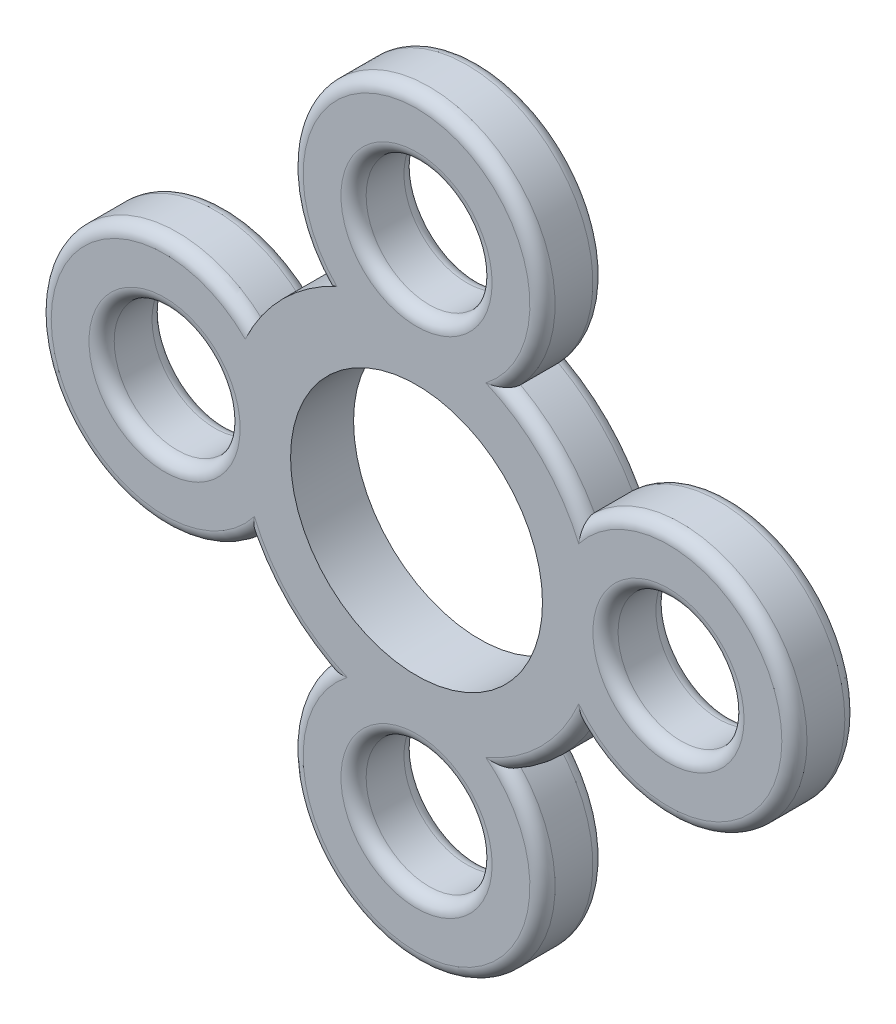
SolidWorks part; units mm, degrees
ref_plane "Front Plane" through (0, 0, 0) normal (0, 0, 1) x (1, 0, 0)
ref_plane "Top Plane" through (0, 0, 0) normal (0, 1, 0) x (1, 0, 0)
ref_plane "Right Plane" through (0, 0, 0) normal (1, 0, 0) x (0, 0, -1)
sketch "Sketch2" plane through (0, 0, 0) normal (0, 0, 1) x (1, 0, 0)
  circle A0 centre (0, 0) radius 10
  arc A1 (-7.2618, 13.125) -> (-13.125, 7.2618) centre (0, 0) ccw
  arc A2 (7.2618, 13.125) -> (-7.2618, 13.125) centre (0, 20) ccw
  arc A3 (13.125, -7.2618) -> (13.125, 7.2618) centre (20, 0) ccw
  arc A4 (-7.2618, -13.125) -> (7.2618, -13.125) centre (0, -20) ccw
  arc A5 (-13.125, 7.2618) -> (-13.125, -7.2618) centre (-20, 0) ccw
  arc A6 (-13.125, -7.2618) -> (-7.2618, -13.125) centre (0, 0) ccw
  arc A7 (13.125, 7.2618) -> (7.2618, 13.125) centre (0, 0) ccw
  arc A8 (7.2618, -13.125) -> (13.125, -7.2618) centre (0, 0) ccw
  circle A9 centre (0, 20) radius 5
  circle A10 centre (20, 0) radius 5
  circle A11 centre (0, -20) radius 5
  circle A12 centre (-20, 0) radius 5
  dimension "D1" = 20
  dimension "D2" = 30
  dimension "D4" = 20
  dimension "D6" = 20
  dimension "D9" = 20
  dimension "D10" = 20
  dimension "D11" = 10
  dimension "D12" = 10
  dimension "D13" = 10
  dimension "D14" = 10
  dimension "D3" = 20
  dimension "D5" = 20
  dimension "D7" = 20
  dimension "D8" = 20
extrude "Boss-Extrude1" add sketch "Sketch2" along normal blind 2.5
fillet "Fillet1" radius 1 1 edges at (0, 30, 2.5)
fillet "Fillet2" radius 1 1 edges at (10.2296, 10.9706, 2.5)
fillet "Fillet3" radius 1 5 edges at (-30, 0, 2.5) (-10.6066, -10.6066, 2.5) (0, -30, 2.5) (10.6066, -10.6066, 2.5) (29.9862, 0.5261, 2.5)
mirror "Mirror2" about plane through (0, 10, 0) normal (0, 0, 1) of bodies 101
fillet "Fillet4" radius 1 8 edges at (5, 20, -2.5) (-15, 0, -2.5) (5, -20, -2.5) (25, 0, -2.5) (25, 0, 2.5) (5, -20, 2.5) (-15, 0, 2.5) (5, 20, 2.5)
